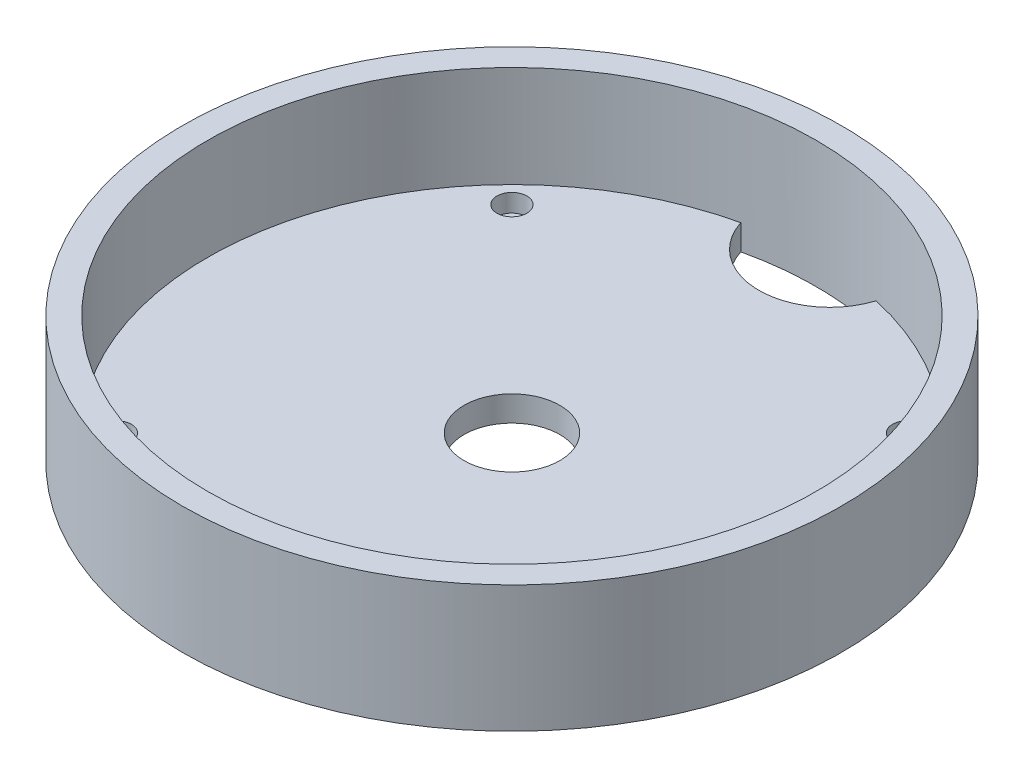
SolidWorks part; units mm, degrees
ref_plane "Front Plane" through (0, 0, 0) normal (0, 0, 1) x (1, 0, 0)
ref_plane "Top Plane" through (0, 0, 0) normal (0, 1, 0) x (1, 0, 0)
ref_plane "Right Plane" through (0, 0, 0) normal (1, 0, 0) x (0, 0, -1)
sketch "Sketch1" plane through (0, 0, 0) normal (0, 1, 0) x (1, 0, 0)
  line L0 (-16.9561, 74.2895) -> (0, 0) construction
  line L1 (0, 0) -> (16.9561, 74.2895) construction
  line L2 (0, 82.55) -> (49.1964, 82.55) construction
  circle A0 centre (0, 0) radius 76.2
  circle A1 centre (0, 0) radius 82.55
  circle A3 centre (0, 0) radius 12
  arc A4 (-16.9561, 74.2895) -> (16.9561, 74.2895) centre (0, 79.6392) ccw
  point P4 (0, 64.5108)
  point P5 (0, 86.8468)
  dimension "D1" = 152.4
  dimension "D2" = 165.1
  dimension "D3" = 24
  dimension "D5" = 25.714
  dimension "D4" = 17.78
extrude "Boss-Extrude1" add sketch "Sketch1" against normal blind 6.35 contours A0 A3 | A1 A0 region at (-46.1745, 0, 57.901) region at (-80.2151, 0, 0)
extrude "Boss-Extrude2" add sketch "Sketch1<3>" along normal blind 25.4 contours A1 A0 region at (-80.2151, 0, 0)
sketch "Sketch1<3>" plane through (0, 0, 0) normal (0, 1, 0) x (1, 0, 0) same geometry as "Sketch1"
sketch "Sketch2" plane through (0, 25.4, 0) normal (0, 1, 0) x (1, 0, 0)
  circle A0 centre (0, 0) radius 82.55
  circle A1 centre (0, 0) radius 92.075
  circle A2 centre (0, 0) radius 76.2
  dimension "D1" = 165.1
  dimension "D2" = 184.15
  dimension "D3" = 152.4
sketch "Sketch5" plane through (0, 0, 0) normal (0, 1, 0) x (1, 0, 0)
  circle A0 centre (-49.53, -49.53) radius 3.75
  circle A1 centre (-49.53, 49.53) radius 3.75
  circle A2 centre (49.53, 49.53) radius 3.75
  circle A3 centre (49.53, -49.53) radius 3.75
  circle A4 centre (-49.53, 49.53) radius 2.25
  circle A5 centre (49.53, 49.53) radius 2.25
  circle A6 centre (49.53, -49.53) radius 2.25
  circle A7 centre (-49.53, -49.53) radius 2.25
  point P2 (0, 0)
  point P6 (0, 0)
  point P13 (0, 0)
  point P16 (0, 0)
  point P21 (0, 0)
  point P23 (0, 0)
  dimension "D1" = 7.5
  dimension "D4" = 4.5
  dimension "D3" = 99.06
  dimension "D2" = 4
  dimension "D5" = 4
extrude "Cut-Extrude1" cut sketch "Sketch5" against normal blind 4.5 contours A1 A4 | A2 A5 | A3 A6 | A0 A7 region at (-53.1739, 0, 49.53) region at (-53.1739, 0, -49.53) region at (45.8861, 0, -49.53) region at (45.8861, 0, 49.53)
extrude "Cut-Extrude2" cut sketch "Sketch5<4>" against normal blind 12.7 contours A7 | A6 | A5 | A4 region at (-49.53, 0, -49.53) region at (49.53, 0, -49.53) region at (49.53, 0, 49.53) region at (-49.53, 0, 49.53)
sketch "Sketch5<4>" plane through (0, 0, 0) normal (0, 1, 0) x (1, 0, 0) same geometry as "Sketch5"
